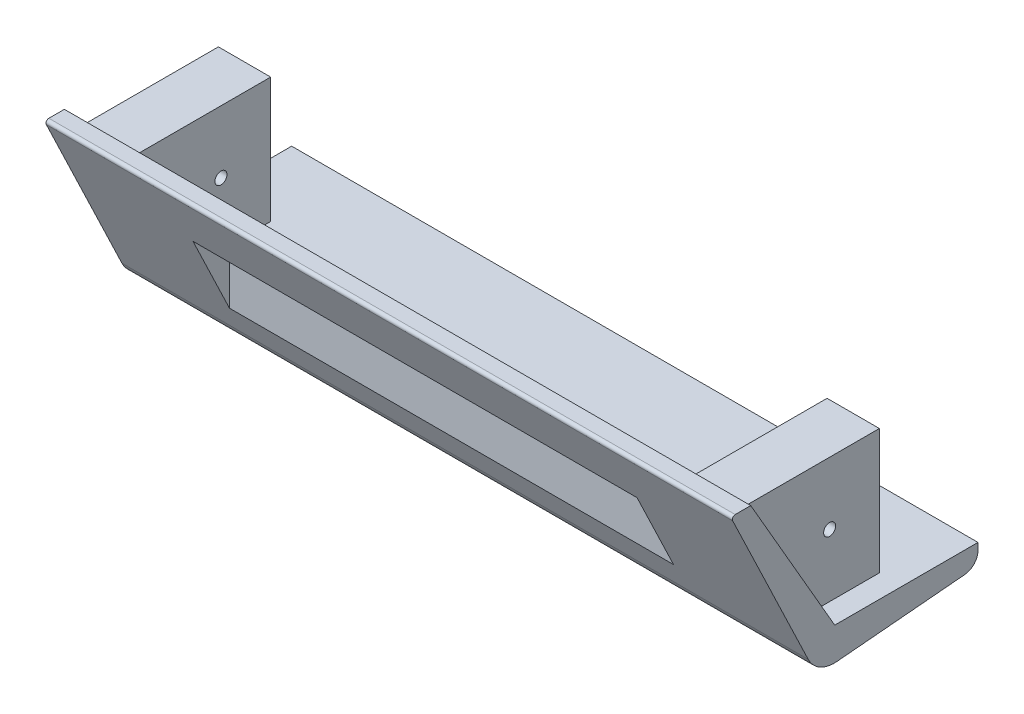
SolidWorks part; units mm, degrees
ref_plane "Front Plane" through (0, 0, 0) normal (0, 0, 1) x (1, 0, 0)
ref_plane "Top Plane" through (0, 0, 0) normal (0, 1, 0) x (1, 0, 0)
ref_plane "Right Plane" through (0, 0, 0) normal (1, 0, 0) x (0, 0, -1)
sketch "Sketch1" plane through (0, 0, 0) normal (1, 0, 0) x (0, 0, -1)
  line L0 (0, 0) -> (-29.3294, 50.8)
  line L1 (0, 0) -> (50, 0)
  line L2 (-29.3294, 50.8) -> (-36.3294, 50.8)
  line L3 (-36.3294, 50.8) -> (-6.2529, -12)
  line L4 (-6.2529, -12) -> (50, -7)
  line L5 (50, -7) -> (50, 0)
  line L6 (-6.2529, -12) -> (-6.2529, 0) construction
  line L7 (-12, 0) -> (0, 0) construction
  dimension "D1" = 50
  dimension "D2" = 60
  dimension "D3" = 50.8
  dimension "D4" = 7
  dimension "D5" = 7
  dimension "D6" = 12
extrude "Boss-Extrude2" add sketch "Sketch1" along normal mid plane 239.55
sketch "Sketch2" plane through (0, 0, 0) normal (0, 0, 1) x (1, 0, 0)
  line L0 (0, 0) -> (0, 50.8) construction
  line L5 (115.75, 47.625) -> (96.7, 47.625) construction
  line L6 (115.75, 47.625) -> (115.75, 3.175) construction
  line L11 (115.75, 3.175) -> (96.7, 3.175) construction
  line L12 (96.7, 47.625) -> (96.7, 3.175) construction
  line L14 (115.35, 47.225) -> (115.35, 3.575)
  line L15 (115.35, 3.575) -> (97.1, 3.575)
  line L28 (97.1, 47.225) -> (97.1, 3.575)
  line L29 (115.35, 47.225) -> (97.1, 47.225)
  line L30 (-96.7, 47.625) -> (-96.7, 3.175) construction
  line L31 (-115.75, 3.175) -> (-96.7, 3.175) construction
  line L32 (-115.75, 47.625) -> (-115.75, 3.175) construction
  line L33 (-115.75, 47.625) -> (-96.7, 47.625) construction
  line L34 (-115.35, 47.225) -> (-97.1, 47.225)
  line L35 (-97.1, 47.225) -> (-97.1, 3.575)
  line L36 (-115.35, 3.575) -> (-97.1, 3.575)
  line L37 (-115.35, 47.225) -> (-115.35, 3.575)
  line L39 (119.775, 0) -> (-119.775, 0) construction
  line L40 (119.775, 50.8) -> (-119.775, 50.8) construction
  line L41 (119.775, 0) -> (119.775, 50.8) construction
  dimension "D2" = 19.05
  dimension "D3" = 44.45
  dimension "D6" = 3.175
  dimension "D4" = 3.175
  dimension "D7" = 4.025
  dimension "D1" = 193.4
  dimension "D5" = 0.4
extrude "Boss-Extrude1" add sketch "Sketch2" along normal up to surface and the other way blind 20 up to face at (0, 25.4, 14.6647)
sketch "Sketch4" plane through (0, 0, 0) normal (1, 0, 0) x (0, 0, -1)
  line L1 (-26.7297, 30.7556) -> (-20, 34.641)
  line L2 (-36.3294, 50.8) -> (-6.2529, -12) construction
  line L3 (0, 0) -> (-29.3294, 50.8) construction
  line L4 (-20, 34.641) -> (-14, 24.2487)
  line L5 (-14, 24.2487) -> (-14, 4.176)
  line L8 (-26.7297, 30.7556) -> (-14, 4.176)
  dimension "D1" = 12
  dimension "D2" = 14
extrude "Cut-Extrude2" cut sketch "Sketch4" against normal mid plane 155
fillet "Fillet1" radius 10 1 edges at (0, -12, 6.2529)
fillet "Fillet2" radius 5 1 edges at (0, -7, -50)
fillet "Fillet3" radius 1 1 edges at (0, 50.8, 36.3294)
hole_wizard "Tap Drill for M5x0.8 Tap1" positions "Sketch11" profile "Sketch6" hole size "M5x0.8" standard "ANSI Metric" end condition through all
sketch "Sketch11" plane through (115.35, 0, 0) normal (1, 0, 0) x (0, 0, -1)
  line L2 (20, 47.225) -> (20, 3.575) construction
  circle A1 centre (2.6405, 25.4) radius 2.1 construction
  point P0 (2.6405, 25.4)
  point P37 (0, 0)
  point P38 (0, 0)
  point P39 (0, 0)
  point P40 (0, 0)
  point P41 (0, 0)
  point P42 (0, 0)
  point P43 (0, 0)
  point P44 (0, 0)
  point P45 (0, 0)
  point P46 (0, 0)
sketch "Sketch6" plane through (115.35, 25.4, -2.6405) normal (0, 1, 0) x (0, 0, -1)
  line L0 (0, 0) -> (0, 235.125)
  line L1 (0, 235.125) -> (2.1, 235.125)
  line L2 (2.1, 235.125) -> (2.1, 0)
  line L5 (2.1, 0) -> (0, 0)
  line L11 (0, -20.4658) -> (0, 143.2542) construction
  point P3 (0, 0)
  point P4 (0, -20.4658)
  point P5 (0, 0)
  point P7 (0, 0)
  point P8 (0, 143.2542)
  dimension "Thru Hole Dia." = 4.2
  dimension "Thru Hole Depth" = 235.125
sketch "Sketch8" plane through (77.5, 0, 0) normal (-1, 0, 0) x (0, 0, 1)
  line L0 (20, 34.641) -> (22.5981, 33.141)
  line L1 (20, 34.641) -> (26.7297, 30.7556) construction
  line L2 (22.5981, 33.141) -> (17.5981, 24.4808)
  line L3 (14.866, 23.7487) -> (14, 24.2487)
  line L4 (14, 24.2487) -> (20, 34.641) construction
  line L5 (20, 34.641) -> (14, 24.2487)
  arc A0 (17.5981, 24.4808) -> (14.866, 23.7487) centre (15.866, 25.4808) cw
  dimension "D2" = 2
  dimension "D1" = 3
extrude "Cut-Extrude3" cut sketch "Sketch8" against normal blind 10
equation "\"D1@Sketch2\"=187.05mm+0.25in"
equation "\"RailSpacing\"= 188.75mm"
equation "\"D1@Boss-Extrude2\"=\"RailSpacing\"+2in"
